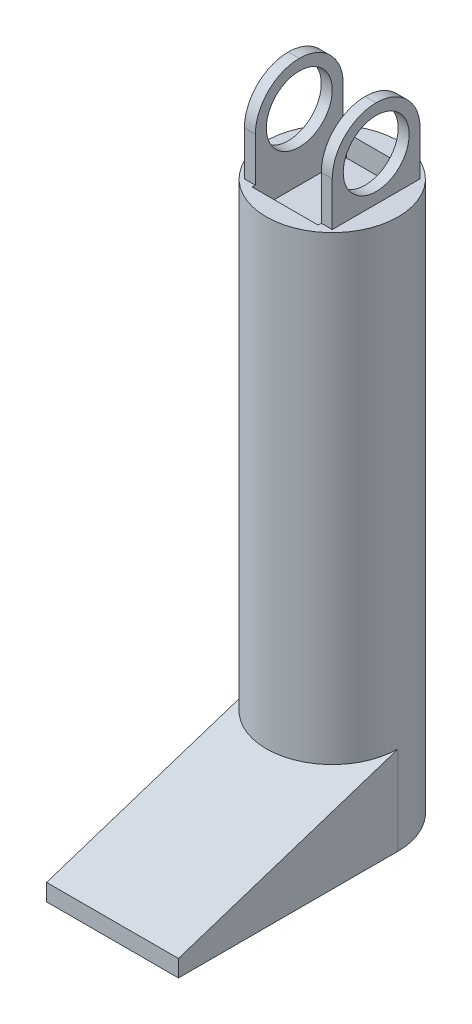
SolidWorks part; units mm, degrees
ref_plane "Front Plane" through (0, 0, 0) normal (0, 0, 1) x (1, 0, 0)
ref_plane "Top Plane" through (0, 0, 0) normal (0, 1, 0) x (1, 0, 0)
ref_plane "Right Plane" through (0, 0, 0) normal (1, 0, 0) x (0, 0, -1)
sketch "Sketch1" plane through (0, 0, 0) normal (0, 1, 0) x (1, 0, 0)
  circle A0 centre (0, 0) radius 3
extrude "Boss-Extrude1" add sketch "Sketch1" along normal blind 25
sketch "Sketch2" plane through (0, 25, 0) normal (0, 1, 0) x (1, 0, 0)
  line L0 (-1.5, 1.5) -> (-1.5, -1.5)
  line L1 (2, 2) -> (-2, 2)
  line L2 (2, 2) -> (2, -2)
  line L3 (2, -2) -> (-2, -2)
  line L4 (-2, 2) -> (-2, -2)
  line L5 (2, 2) -> (-2, -2) construction
  line L6 (2, -2) -> (-2, 2) construction
  line L7 (1.5, -1.5) -> (-1.5, -1.5)
  line L8 (1.5, 1.5) -> (1.5, -1.5)
  line L9 (1.5, 1.5) -> (-1.5, 1.5)
  point P0 (0, 0)
  dimension "D1" = 4
  dimension "D2" = 4
  dimension "D3" = 0.5
extrude "Boss-Extrude2" add sketch "Sketch2" along normal blind 4
sketch "Sketch3" plane through (0, 29, 0) normal (0, 1, 0) x (1, 0, 0)
  line L1 (1.5, 2.1441) -> (-1.5, 2.1441)
  line L2 (1.5, 2.1441) -> (1.5, -2.1441)
  line L3 (1.5, -2.1441) -> (-1.5, -2.1441)
  line L4 (-1.5, 2.1441) -> (-1.5, -2.1441)
  line L5 (1.5, 2.1441) -> (-1.5, -2.1441) construction
  line L6 (1.5, -2.1441) -> (-1.5, 2.1441) construction
  point P0 (0, 0)
extrude "Cut-Extrude1" cut sketch "Sketch3" against normal blind 5
sketch "Sketch4" plane through (-2, 0, 0) normal (-1, 0, 0) x (0, 0, 1)
  line L0 (0, 29) -> (0, 27)
  line L1 (-2, 29) -> (2, 29) construction
  circle A0 centre (0, 27) radius 1.5
extrude "Cut-Extrude2" cut sketch "Sketch4" against normal blind 5 contours A0 region at (-2, 25.9693, -1.0307)
fillet "Fillet1" radius 2 4 edges at (1.75, 29, 2) (1.75, 29, -2) (-1.75, 29, -2) (-1.75, 29, 2)
sketch "Sketch5" plane through (0, 0, 0) normal (0, 0, 1) x (1, 0, 0)
  line L1 (3, 4.0329) -> (-3, 4.0329)
  line L2 (3, 4.0329) -> (3, 0)
  line L3 (3, 0) -> (-3, 0)
  line L4 (-3, 4.0329) -> (-3, 0)
  line L5 (3, 4.0329) -> (-3, 0) construction
  line L6 (3, 0) -> (-3, 4.0329) construction
  point P0 (0, 2.0164)
extrude "Boss-Extrude3" add sketch "Sketch5" along normal blind 10
sketch "Sketch6" plane through (-3, 0, 0) normal (-1, 0, 0) x (0, 0, 1)
  line L0 (10, 0) -> (10, 0.7692)
  line L1 (10, 4.0329) -> (10, 0) construction
  line L2 (10, 0.7692) -> (0, 4.0329)
  line L3 (0, 4.0329) -> (0, 4.695)
  line L4 (0, 4.695) -> (10, 4.695)
  line L5 (10, 4.695) -> (10, 0.7692)
  line M7 (10, 0) -> (10, 4.0329)
  line M8 (10, 4.0329) -> (0, 4.0329)
extrude "Cut-Extrude4" cut sketch "Sketch6" against normal blind 10 contours L2 M7 M8 region at (-3, 2.945, 6.6667)
